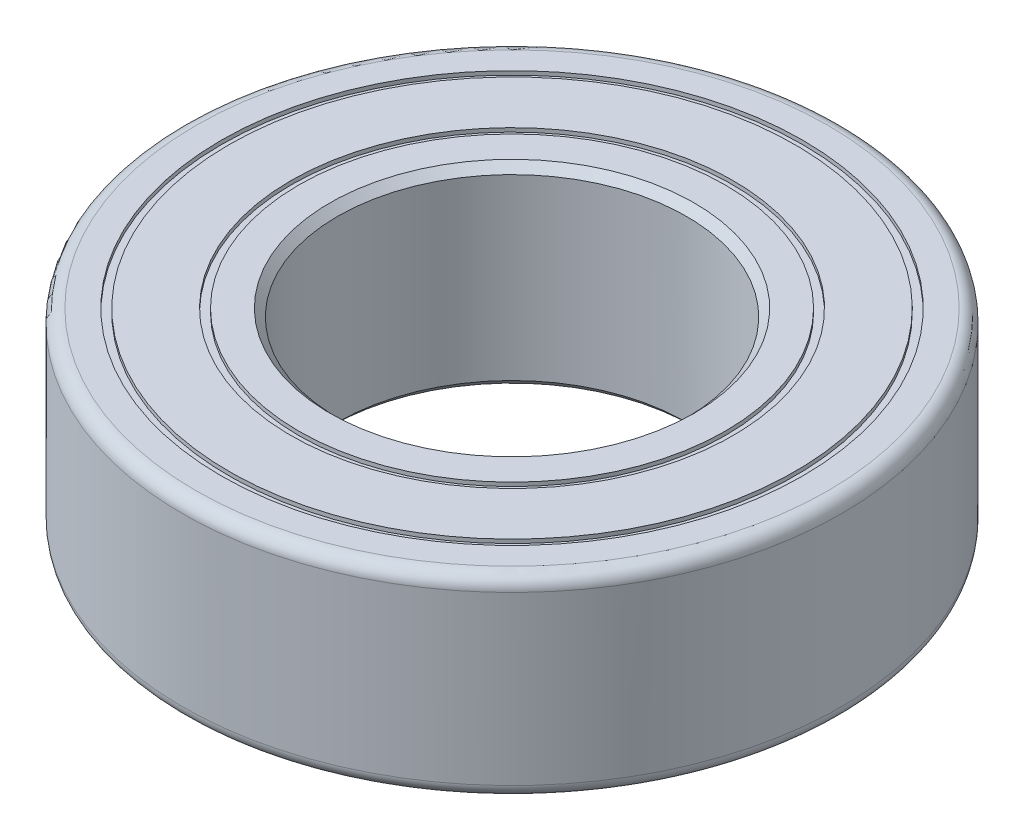
SolidWorks part; units mm, degrees
ref_plane "Front Plane" through (0, 0, 0) normal (0, 0, 1) x (1, 0, 0)
ref_plane "Top Plane" through (0, 0, 0) normal (0, 1, 0) x (1, 0, 0)
ref_plane "Right Plane" through (0, 0, 0) normal (1, 0, 0) x (0, 0, -1)
sketch "Sketch1" plane through (0, 0, 0) normal (0, 0, 1) x (1, 0, 0)
  line L0 (0, 0) -> (4.5, 0) construction
  line L1 (8.5, 0) -> (8.5, 5)
  line L3 (0, 2.5) -> (0, 0) construction
  line L4 (4.5, 0) -> (4.5, 5)
  line L5 (4.5, 0) -> (5.5, 0)
  line L6 (5.5, 0) -> (5.5, 0.1)
  line L7 (5.5, 0.1) -> (5.7, 0.1)
  line L8 (5.7, 0.1) -> (5.7, 0)
  line L9 (5.7, 0) -> (7.3, 0)
  line L10 (6.5, 0) -> (6.5, 2.5) construction
  line L11 (8.5, 2.5) -> (4.5, 2.5) construction
  line L12 (4.5, 2.5) -> (0, 2.5) construction
  line L13 (7.3, 0.1) -> (7.3, 0)
  line L14 (7.5, 0.1) -> (7.3, 0.1)
  line L15 (7.5, 0) -> (7.5, 0.1)
  line L16 (8.5, 0) -> (7.5, 0)
  line L17 (8.5, 5) -> (7.5, 5)
  line L18 (7.5, 5) -> (7.5, 4.9)
  line L19 (7.5, 4.9) -> (7.3, 4.9)
  line L20 (7.3, 4.9) -> (7.3, 5)
  line L21 (5.7, 5) -> (7.3, 5)
  line L22 (5.7, 4.9) -> (5.7, 5)
  line L23 (5.5, 4.9) -> (5.7, 4.9)
  line L24 (5.5, 5) -> (5.5, 4.9)
  line L25 (4.5, 5) -> (5.5, 5)
  dimension "D1" = 8.5
  dimension "D2" = 4.5
  dimension "D4" = 1
  dimension "D5" = 0.2
  dimension "D6" = 0.1
  dimension "D3" = 5
revolve "Revolve1" add sketch "Sketch1" angle 360 about L3
fillet "Fillet2" radius 0.344 2 edges at (-8.5, 0, 0) (-8.5, 5, 0)
chamfer "Chamfer2" distance 0.2 angle 45 2 edges at (-4.5, 0, 0) (-4.5, 5, 0)
equation "\"Ratio\"= 15"
equation "\"Hull Diameter\"= 3.5in"
equation "\"Fixed Ring Diameter\"= 76"
equation "\"Fixed Pin Diameter\"= 6"
equation "\"Output Ring Diameter\"= 40"
equation "\"Output Pin Diameter\"= 6"
equation "\"Disk Bearing Inner Diameter\"= 9"
equation "\"Disk Bearing Outer Diameter\"= 17"
equation "\"Disk Bearing Height\"= 5"
equation "\"Shaft Bearing Inner Diameter\"= 15"
equation "\"Shaft Bearing Outer Diameter\"= 21"
equation "\"Shaft Bearing Height\"= 4"
equation "\"Eccentricity\"= 1.5"
equation "\"Disk Height\"= 8"
equation "\"Disk Spacing\"= 5"
equation "\"Hull Height\"= 40"
equation "\"Shaft End Bearing Inner Diameter\"= 12"
equation "\"Shaft End Bearing Outer Diameter\"= 18"
equation "\"Shaft End Bearing Height\"= 4"
equation "\"Output Bearing Inner Diameter\"= 55"
equation "\"Output Bearing Outer Diameter\"= 72"
equation "\"Outer Bearing Height\"= 9"
equation "\"D3@Sketch1\"= \"Disk Bearing Height\""
equation "\"D2@Sketch1\" = \"Disk Bearing Inner Diameter\" / 2"
equation "\"D1@Sketch1\" = \"Disk Bearing Outer Diameter\" / 2"
